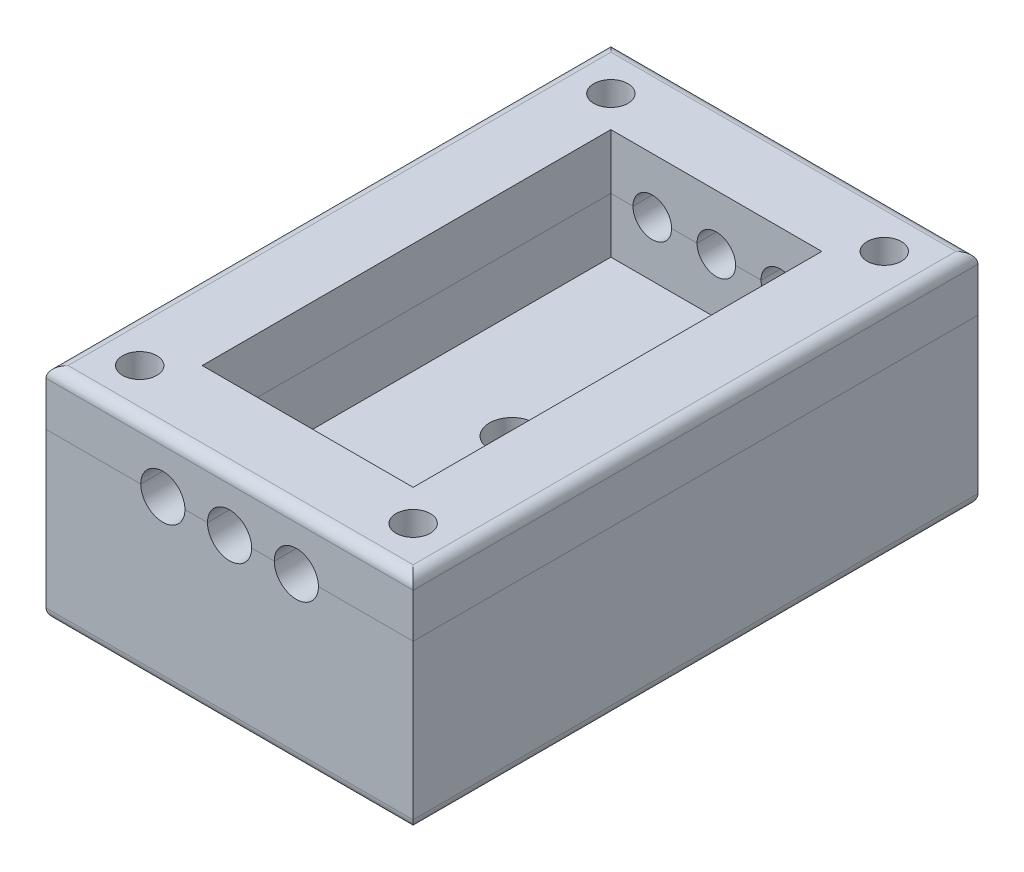
SolidWorks part; units mm, degrees
note: The reader was unsure of these and kept them because the rebuilt part matched: shared geometry of "Esquisse3<3>".
ref_plane "Plan de face" through (0, 0, 0) normal (0, 0, 1) x (1, 0, 0)
ref_plane "Plan de dessus" through (0, 0, 0) normal (0, 1, 0) x (1, 0, 0)
ref_plane "Plan de droite" through (0, 0, 0) normal (1, 0, 0) x (0, 0, -1)
sketch "Esquisse1" plane through (0, 0, 0) normal (0, 0, 1) x (1, 0, 0)
  line L0 (0, 4) -> (0, 14.517) construction
  line L1 (-2.95, 10.1031) -> (2.95, 10.1031)
  line L22 (2.95, 10.1031) -> (2.95, 8.4831)
  line L23 (2.95, 8.4831) -> (5.71, 8.4831)
  line L24 (5.71, 8.4831) -> (5.71, 6.9831)
  line L25 (5.71, 6.9831) -> (3.5, 4.84)
  line L26 (3.5, 4.84) -> (-3.5, 4.84)
  line L27 (-5.71, 6.9831) -> (-3.5, 4.84)
  line L28 (-5.71, 8.4831) -> (-5.71, 6.9831)
  line L29 (-2.95, 8.4831) -> (-5.71, 8.4831)
  line L30 (-2.95, 10.1031) -> (-2.95, 8.4831)
  point P10 (0, 4.84)
  point P14 (0, 10.1031)
  point P41 (0, 0)
  point P46 (0, 0)
  line B0 (0, 0) -> (0, 4) construction
  line B1 (0, 4) -> (0.866, 4.5)
  line B2 (0, 4) -> (-0.866, 4.5)
  line B3 (0.866, 4.5) -> (3.4393, 4.5)
  line B4 (3.4393, 4.5) -> (6, 7.0607)
  line B5 (6, 7.0607) -> (6, 8.5)
  line B6 (6, 8.5) -> (3, 8.5)
  line B7 (3, 8.5) -> (3, 9.5)
  line B8 (3, 9.5) -> (3.5, 9.5)
  line B9 (3.5, 9.5) -> (3.5, 10)
  line B10 (3.5, 10) -> (8.5, 10)
  line B11 (0, 0) -> (1.2745, 0) construction
  line B12 (-3.5, -10) -> (-8.5, -10)
  line B13 (-3.4393, -4.5) -> (-6, -7.0607)
  line B14 (-3.5, 9.5) -> (-3.5, 10)
  line B15 (-3, 9.5) -> (-3.5, 9.5)
  line B16 (-3, 8.5) -> (-3, 9.5)
  line B17 (-6, 8.5) -> (-3, 8.5)
  line B18 (-6, 7.0607) -> (-6, 8.5)
  line B19 (-0.866, 4.5) -> (-3.4393, 4.5)
  line B20 (-3.4393, 4.5) -> (-6, 7.0607)
  line B21 (-3.5, 10) -> (-8.5, 10)
  line B22 (-0.866, -4.5) -> (-3.4393, -4.5)
  line B23 (-6, -7.0607) -> (-6, -8.5)
  line B24 (-6, -8.5) -> (-3, -8.5)
  line B25 (-3, -8.5) -> (-3, -9.5)
  line B26 (-3, -9.5) -> (-3.5, -9.5)
  line B27 (-3.5, -9.5) -> (-3.5, -10)
  line B28 (3.5, -10) -> (8.5, -10)
  line B29 (3.5, -9.5) -> (3.5, -10)
  line B30 (3, -9.5) -> (3.5, -9.5)
  line B31 (3, -8.5) -> (3, -9.5)
  line B32 (6, -8.5) -> (3, -8.5)
  line B33 (6, -7.0607) -> (6, -8.5)
  line B34 (3.4393, -4.5) -> (6, -7.0607)
  line B35 (0.866, -4.5) -> (3.4393, -4.5)
  line B36 (0, -4) -> (-0.866, -4.5)
  line B37 (0, -4) -> (0.866, -4.5)
  line B38 (10, -3.5) -> (10, -8.5)
  line B39 (9.5, -3.5) -> (10, -3.5)
  line B40 (8.5, -3) -> (9.5, -3)
  line B41 (9.5, -3) -> (9.5, -3.5)
  line B42 (8.5, -6) -> (8.5, -3)
  line B43 (7.0607, -6) -> (8.5, -6)
  line B44 (4.5, -3.4393) -> (7.0607, -6)
  line B45 (4.5, -0.866) -> (4.5, -3.4393)
  line B46 (4.5, 0.866) -> (4.5, 3.4393)
  line B47 (4.5, 3.4393) -> (7.0607, 6)
  line B48 (7.0607, 6) -> (8.5, 6)
  line B49 (8.5, 6) -> (8.5, 3)
  line B50 (8.5, 3) -> (9.5, 3)
  line B51 (9.5, 3) -> (9.5, 3.5)
  line B52 (9.5, 3.5) -> (10, 3.5)
  line B53 (10, 3.5) -> (10, 8.5)
  line B54 (-3.5, -9.5) -> (-3.5, -10)
  line B55 (-3, -8.5) -> (-3, -9.5)
  line B56 (-3, -9.5) -> (-3.5, -9.5)
  line B57 (-6, -8.5) -> (-3, -8.5)
  line B58 (-6, -7.0607) -> (-6, -8.5)
  line B59 (-3.4393, -4.5) -> (-6, -7.0607)
  line B60 (-0.866, -4.5) -> (-3.4393, -4.5)
  line B61 (0.866, -4.5) -> (3.4393, -4.5)
  line B62 (3.4393, -4.5) -> (6, -7.0607)
  line B63 (6, -7.0607) -> (6, -8.5)
  line B64 (6, -8.5) -> (3, -8.5)
  line B65 (3, -8.5) -> (3, -9.5)
  line B66 (3, -9.5) -> (3.5, -9.5)
  line B67 (3.5, -9.5) -> (3.5, -10)
  line B68 (-10, 3.5) -> (-10, 8.5)
  line B69 (-9.5, 3.5) -> (-10, 3.5)
  line B70 (-8.5, 3) -> (-9.5, 3)
  line B71 (-9.5, 3) -> (-9.5, 3.5)
  line B72 (-8.5, 6) -> (-8.5, 3)
  line B73 (-7.0607, 6) -> (-8.5, 6)
  line B74 (-4.5, 3.4393) -> (-7.0607, 6)
  line B75 (-4.5, 0.866) -> (-4.5, 3.4393)
  line B76 (-4.5, -0.866) -> (-4.5, -3.4393)
  line B77 (-4.5, -3.4393) -> (-7.0607, -6)
  line B78 (-7.0607, -6) -> (-8.5, -6)
  line B79 (-8.5, -6) -> (-8.5, -3)
  line B80 (-8.5, -3) -> (-9.5, -3)
  line B81 (-9.5, -3) -> (-9.5, -3.5)
  line B82 (-9.5, -3.5) -> (-10, -3.5)
  line B83 (-10, -3.5) -> (-10, -8.5)
  line B84 (4, 0) -> (4.5, -0.866)
  line B85 (4, 0) -> (4.5, 0.866)
  line B86 (0, -4) -> (-0.866, -4.5)
  line B87 (0, -4) -> (0.866, -4.5)
  line B88 (-4, 0) -> (-4.5, 0.866)
  line B89 (-4, 0) -> (-4.5, -0.866)
  line B90 (0, 0) -> (1.9445, 1.9445) construction
  arc B91 (8.5, 10) -> (10, 8.5) centre (8.5, 8.5) cw
  arc B92 (-8.5, 10) -> (-10, 8.5) centre (-8.5, 8.5) ccw
  arc B93 (-8.5, -10) -> (-10, -8.5) centre (-8.5, -8.5) cw
  arc B94 (8.5, -10) -> (10, -8.5) centre (8.5, -8.5) ccw
  circle B95 centre (0, 0) radius 2.75
  dimension "D1" = 2.95
  dimension "D2" = 1.62
  dimension "D3" = 2.76
  dimension "D4" = 1.5
  dimension "D5" = 135.88
  dimension "D6" = 3.5
  dimension "D7" = 0.34
sketch_block_instance "Bloc1-1"
sketch_block "Bloc1"
extrude "Boss.-Extru.1" add sketch "Esquisse1" against normal blind 20 contours L0 L26 L25 L24 L23 L22 L1 | L26 L0 L1 L30 L29 L28 L27
fillet "Congé1" radius 0.5 10 edges at (0, 4.84, -20) (-4.605, 5.9116, -20) (-5.71, 7.7331, -20) (4.605, 5.9116, -20) (5.71, 7.7331, -20) (-5.71, 7.7331, 0) (-4.605, 5.9116, 0) (0, 4.84, 0) (4.605, 5.9116, 0) (5.71, 7.7331, 0)
fillet "Congé2" radius 1 6 edges at (5.5636, 7.0451, -0.1464) (5.5636, 7.0451, -19.8536) (-5.5636, 7.0451, -0.1464) (-5.5636, 7.0451, -19.8536) (-5.71, 6.9831, -10) (5.71, 6.9831, -10)
sketch "Esquisse3" plane through (0, 10.1031, 0) normal (0, 1, 0) x (1, 0, 0)
  line L0 (0, 0) -> (0, 20) construction
  line L1 (-2.95, 20) -> (2.95, 20) construction
  line L2 (-9.55, -8.5) -> (-16.6211, -15.5711) construction
  line L3 (-16.6211, 35.5711) -> (16.6211, 35.5711)
  line L4 (-16.6211, 35.5711) -> (-16.6211, -15.5711)
  line L5 (-16.6211, -15.5711) -> (16.6211, -15.5711)
  line L6 (16.6211, 35.5711) -> (16.6211, -15.5711)
  line L7 (-16.6211, 35.5711) -> (16.6211, -15.5711) construction
  line L8 (-16.6211, -15.5711) -> (16.6211, 35.5711) construction
  line L9 (-9.55, 28.5) -> (9.55, 28.5)
  line L10 (-9.55, 28.5) -> (-9.55, -8.5)
  line L11 (-9.55, -8.5) -> (9.55, -8.5)
  line L12 (9.55, 28.5) -> (9.55, -8.5)
  line L13 (-9.55, 28.5) -> (9.55, -8.5) construction
  line L14 (-9.55, -8.5) -> (9.55, 28.5) construction
  line L15 (9.55, -8.5) -> (16.6211, -15.5711) construction
  line L16 (0, 10) -> (-5.1118, 10) construction
  circle A0 centre (-12.3784, -11.3284) radius 1.55
  circle A1 centre (12.3784, -11.3284) radius 1.55
  circle A2 centre (12.3784, 31.3284) radius 1.55
  circle A3 centre (-12.3784, 31.3284) radius 1.55
  point P5 (0, 10)
  point P10 (0, 10)
  dimension "D5" = 3.1
  dimension "D1" = 45
  dimension "D2" = 10
  dimension "D3" = 19.1
  dimension "D4" = 37
  dimension "D6" = 4
extrude "Boss.-Extru.2" add sketch "Esquisse3" along normal blind 10 contours A3 | A2 | L6 L3 L4 L5 A1 A0 L9 L12 L11 L10 A2 A3 | L12 L9 L10 L11 L2 A1 L0 A0 | A1 L2 A0 L0 | A0 | A1
extrude "Boss.-Extru.4" add sketch "Esquisse3<3>" along normal blind 20
sketch "Esquisse3<3>" plane through (0, 10.1031, 0) normal (0, 1, 0) x (1, 0, 0) same geometry as "Esquisse3"
sketch "Esquisse8" plane through (0, 0, -28.5) normal (0, 0, 1) x (1, 0, 0)
  line L0 (-9.55, 20.1031) -> (9.55, 20.1031) construction
  line L1 (9.55, 20.1031) -> (9.55, 30.1031) construction
  line L2 (9.55, 25.1031) -> (5.8, 25.1031) construction
  line L3 (5.8, 25.1031) -> (0, 25.1031) construction
  line L4 (0, 25.1031) -> (-5.8, 25.1031) construction
  circle A0 centre (5.8, 25.1031) radius 1.75
  circle A1 centre (0, 25.1031) radius 1.75
  circle A2 centre (-5.8, 25.1031) radius 1.75
  dimension "D2" = 3.5
  dimension "D4" = 3.5
  dimension "D6" = 3.5
  dimension "D1" = 3.75
  dimension "D3" = 5.8
  dimension "D5" = 5.8
extrude "Trous_moteur" cut sketch "Esquisse8" against normal up to next
sketch "Esquisse5" plane through (0, 0, 0) normal (0, 0, 1) x (1, 0, 0)
  line L0 (-5.21, 8.4831) -> (-5.71, 8.4831) construction
  line L1 (-3.5, 4.84) -> (-5.4062, 6.6885) construction
  line L2 (3.5, 4.84) -> (-3.5, 4.84) construction
  line L3 (5.4062, 6.6885) -> (3.5, 4.84) construction
  line L4 (5.71, 8.4831) -> (5.71, 7.4064) construction
  line L5 (5.71, 8.4831) -> (5.21, 8.4831) construction
  line L6 (2.95, 8.4831) -> (5.21, 8.4831) construction
  line L7 (-2.95, 8.4831) -> (-5.21, 8.4831) construction
  line L8 (-5.71, 7.4064) -> (-5.71, 8.4831) construction
  line L9 (-5.21, 8.4831) -> (-5.71, 8.4831)
  line L10 (-3.5, 4.84) -> (-5.4062, 6.6885)
  line L11 (3.5, 4.84) -> (-3.5, 4.84)
  line L12 (5.4062, 6.6885) -> (3.5, 4.84)
  line L13 (5.71, 8.4831) -> (5.71, 7.4064)
  line L14 (5.71, 8.4831) -> (5.21, 8.4831)
  line L15 (2.95, 8.4831) -> (5.21, 8.4831)
  line L16 (-2.95, 8.4831) -> (-5.21, 8.4831)
  line L17 (-5.71, 7.4064) -> (-5.71, 8.4831)
  line L18 (-2.95, 8.4831) -> (2.95, 8.4831)
  arc A0 (5.4062, 6.6885) -> (5.71, 7.4064) centre (4.71, 7.4064) ccw construction
  arc A1 (-5.71, 7.4064) -> (-5.4062, 6.6885) centre (-4.71, 7.4064) ccw construction
  arc A2 (5.4062, 6.6885) -> (5.71, 7.4064) centre (4.71, 7.4064) ccw
  arc A3 (-5.71, 7.4064) -> (-5.4062, 6.6885) centre (-4.71, 7.4064) ccw
extrude "Enlèv. mat.-Extru.1" cut sketch "Esquisse5" against normal through all
sketch "Esquisse9" plane through (0, 0, 8.5) normal (0, 0, -1) x (-1, 0, 0)
  line L0 (-9.55, 20.1031) -> (9.55, 20.1031) construction
  line L1 (9.55, 20.1031) -> (9.55, 30.1031) construction
  line L2 (9.55, 25.1031) -> (6.045, 25.1031) construction
  line L3 (-9.55, 20.1031) -> (-9.55, 30.1031) construction
  line L4 (-9.55, 25.1031) -> (-6.045, 25.1031) construction
  line L5 (-6.045, 25.1031) -> (6.045, 25.1031) construction
  circle A0 centre (6.045, 25.1031) radius 2
  circle A1 centre (-6.045, 25.1031) radius 2
  circle A2 centre (0, 25.1031) radius 2
  dimension "D2" = 4
  dimension "D4" = 4
  dimension "D5" = 4
  dimension "D1" = 12.09
extrude "Trous_cables_puissance" cut sketch "Esquisse9" against normal up to next
sketch "Esquisse10" plane through (0, 20.1031, 0) normal (0, 1, 0) x (1, 0, 0)
  line L0 (-9.55, -8.5) -> (0, -8.5) construction
  line L1 (9.55, -8.5) -> (-9.55, -8.5) construction
  line L2 (0, -8.5) -> (0, 28.5) construction
  line L3 (-9.55, 28.5) -> (9.55, 28.5) construction
  circle A0 centre (0, 10) radius 2.05
  dimension "D1" = 4.1
extrude "Enlèv. mat.-Extru.4" cut sketch "Esquisse10" against normal up to next contours A0
fillet "Congé3" radius 1 8 edges at (0, 10.1031, 15.5711) (16.6211, 10.1031, -10) (0, 10.1031, -35.5711) (-16.6211, 10.1031, -10) (0, 30.1031, 15.5711) (-16.6211, 30.1031, -10) (0, 30.1031, -35.5711) (16.6211, 30.1031, -10)
sketch "Esquisse11" plane through (0, 0, 15.5711) normal (0, 0, 1) x (1, 0, 0)
  line L0 (-6.045, 25.1031) -> (-16.6211, 25.1031) construction
  line L1 (-16.6211, 29.1031) -> (-16.6211, 11.1031) construction
  line L2 (16.6211, 29.1031) -> (16.6211, 11.1031) construction
  line L3 (-15.6211, 30.1031) -> (15.6211, 30.1031) construction
  line L4 (16.6211, 29.1031) -> (16.6211, 25.1031)
  line L5 (-15.6211, 30.1031) -> (15.6211, 30.1031)
  line L6 (-16.6211, 29.1031) -> (-16.6211, 25.1031)
  line L7 (-16.6211, 25.1031) -> (16.6211, 25.1031)
  arc A0 (16.6211, 29.1031) -> (15.6211, 30.1031) centre (15.6211, 29.1031) ccw construction
  arc A1 (-15.6211, 30.1031) -> (-16.6211, 29.1031) centre (-15.6211, 29.1031) ccw construction
  arc A2 (16.6211, 29.1031) -> (15.6211, 30.1031) centre (15.6211, 29.1031) ccw
  arc A3 (-15.6211, 30.1031) -> (-16.6211, 29.1031) centre (-15.6211, 29.1031) ccw
split "Fractionner1" trim tools "Esquisse11" bodies to split 110 resulting bodies 111 112
equation "\"hole_thickness\"=20"
equation "\"D1@Boss.-Extru.4\"=\"hole_thickness\""
